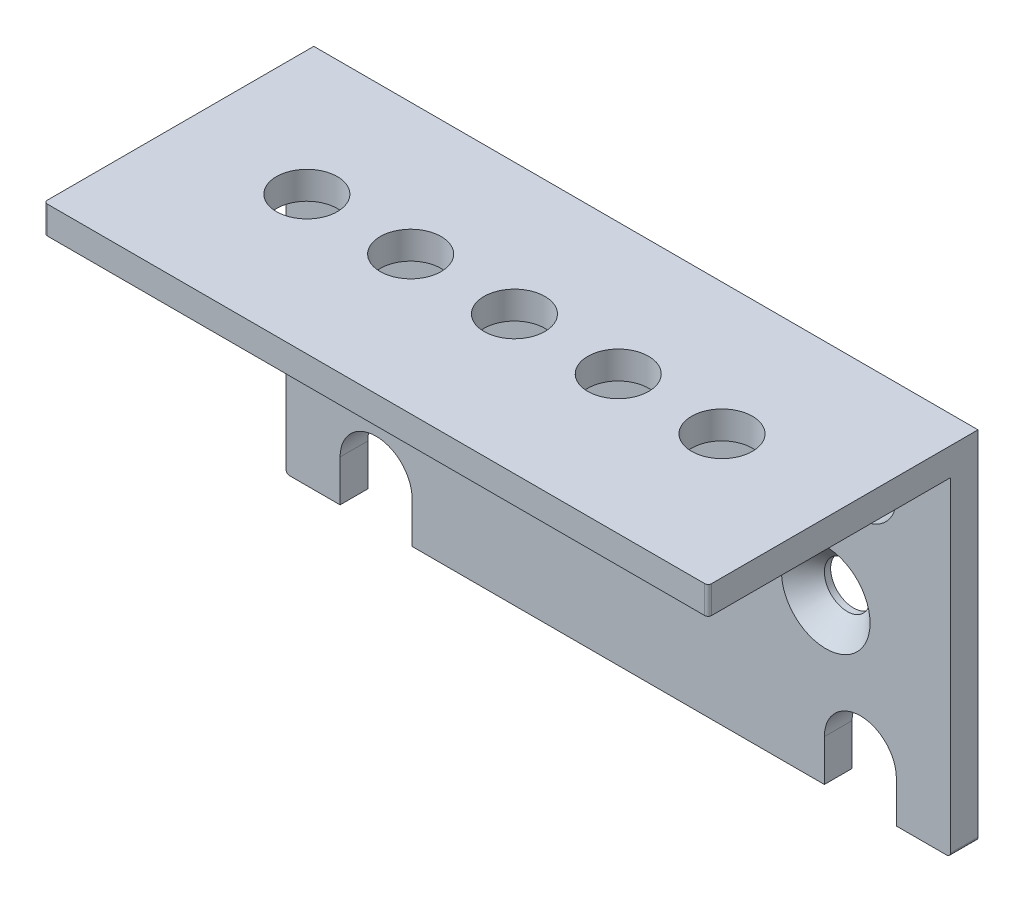
SolidWorks part; units mm, degrees
ref_plane "前视基准面" through (0, 0, 0) normal (0, 0, 1) x (1, 0, 0)
ref_plane "上视基准面" through (0, 0, 0) normal (0, 1, 0) x (1, 0, 0)
ref_plane "右视基准面" through (0, 0, 0) normal (1, 0, 0) x (0, 0, -1)
other "Configuration Table"
sketch "草图1" plane through (0, 0, 0) normal (0, 0, 1) x (1, 0, 0)
  line L0 (0, 0) -> (96, 0)
  line L1 (96, 0) -> (96, -47)
  line L2 (96, -47) -> (0, -47)
  line L3 (0, -47) -> (0, 0)
  dimension "D1" = 96
  dimension "D2" = 47
extrude "凸台-拉伸1" add sketch "草图1" along normal blind 4
sketch "草图2" plane through (0, 0, 4) normal (0, 0, 1) x (1, 0, 0)
  line L0 (96, -23.5) -> (0, -23.5)
  line L1 (96, -47) -> (96, 0) construction
  line L2 (0, 0) -> (0, -47) construction
  line L3 (48, 0) -> (48, -47)
  line L4 (96, 0) -> (0, 0) construction
  line L5 (0, -47) -> (96, -47) construction
  line L6 (48, -23.5) -> (48, -12)
  line L7 (18.2, -41) -> (18.2, -47)
  line L8 (0, -47) -> (96, -47) construction
  line L9 (18.2, -47) -> (7.8, -47)
  line L10 (7.8, -47) -> (7.8, -41)
  line L11 (77.8, -41) -> (77.8, -47)
  line L12 (77.8, -47) -> (88.2, -47)
  line L13 (88.2, -47) -> (88.2, -41)
  circle A0 centre (83, -6) radius 5.2
  circle A1 centre (83, -41) radius 5.2
  circle A2 centre (13, -41) radius 5.2
  circle A3 centre (13, -6) radius 5.2
  circle A4 centre (48, -23.5) radius 2.8224
  circle A5 centre (78, -23.5) radius 2.4023
  circle A6 centre (18, -23.5) radius 3.1016
  line M5 (0, -47) -> (96, -47)
  dimension "D1" = 35
  dimension "D3" = 30
  dimension "D4" = 30
  dimension "D2" = 17.5
sketch "草图8" plane through (0, 0, 4) normal (0, 0, 1) x (1, 0, 0)
  line L5 (48, -47) -> (48, 0)
  line L6 (0, -47) -> (96, -47) construction
  line L7 (96, 0) -> (0, 0) construction
  line L8 (96, -23.5) -> (0, -23.5)
  line L9 (96, -47) -> (96, 0) construction
  line L10 (0, 0) -> (0, -47) construction
  line L11 (48, -23.5) -> (78, -23.5)
  line L12 (48, -23.5) -> (18, -23.5)
  circle A0 centre (18, -23.5) radius 3.3648
  circle A1 centre (48, -23.5) radius 3.7667
  circle A2 centre (78, -23.5) radius 3.2192
  circle A3 centre (63, -23.5) radius 3.2586
  circle A4 centre (33, -23.5) radius 3.1199
  dimension "D3" = 15
  dimension "D1" = 30
  dimension "D2" = 60
  dimension "D4" = 15
sketch "草图12" plane through (0, 0, 0) normal (0, 1, 0) x (1, 0, 0)
  line L0 (0, -4) -> (0, 0)
  line L2 (96, -4) -> (96, 0)
  line L3 (0, -4) -> (96, -4)
  line L4 (0, 0) -> (96, 0)
  line L7 (0, -4) -> (0, -5)
  line L9 (96, 0) -> (96, -39)
  line L10 (0, 0) -> (0, -39)
  line L11 (48, -19) -> (78, -19)
  line L13 (0, -39) -> (96, -39)
  circle A3 centre (18, -19) radius 4.4
  circle A4 centre (78, -19) radius 4.4
  circle A5 centre (48, -19) radius 4.4
  circle A6 centre (63, -19) radius 4.4
  circle A7 centre (33, -19) radius 4.4
  line M7 (96, 0) -> (0, 0)
  line M8 (0, 0) -> (0, -4)
  line M9 (0, -4) -> (96, -4)
  line M10 (96, -4) -> (96, 0)
  dimension "D1" = 39
  dimension "D2" = 60
  dimension "D3" = 15
  dimension "D4" = 30
  dimension "D5" = 48
extrude "凸台-拉伸3" add sketch "草图12" along normal blind 4.5 contours L0 L3 M10 M7 M8 M9 | A6 A4 A5 L10 L13 L9 L3 A3 A7 M9 region at (48, 0, 2) region at (48, 0, 5.0218)
sketch "草图13" plane through (0, -47, 0) normal (0, -1, 0) x (1, 0, 0)
  line L0 (0, 4) -> (0, 0)
  line L1 (0, 0) -> (96, 0)
  line L2 (96, 0) -> (96, 4)
  line L3 (96, 4) -> (0, 4)
extrude "切除-拉伸1" cut sketch "草图12<4>" along normal blind 0.5 contours A6 A4 A5 L10 L13 L9 L3 A3 A7 M9 region at (48, 0, 5.0218)
sketch "草图12<4>" plane through (0, 0, 0) normal (0, 1, 0) x (1, 0, 0) same geometry as "草图12"
extrude "切除-拉伸2" cut sketch "草图2" against normal blind 10 contours A3 | A2 | A1 | A0 | L13 A1 L11 M5 | A2 L10 L7 M5 | A2 region at (77.9201, -44, 4) region at (13, -46.8799, 4) region at (13, -41, 4) region at (83, -41, 4) region at (83, -6, 4) region at (13, -6, 4)
hole_wizard "M6 内六角花形沉头螺钉的锥形沉头孔1" positions "草图14" profile "草图15" countersink size "M6" standard "GB" end condition through all
sketch "草图14" plane through (0, 0, 4) normal (0, 0, 1) x (1, 0, 0)
  point P0 (18, -23.5)
  point P3 (48, -23.5)
  point P6 (78, -23.5)
sketch "草图15" plane through (18, -23.5, 4) normal (1, 0, 0) x (0, -1, 0)
  line L0 (0, 0) -> (0, 4)
  line L1 (0, 4) -> (3.3, 4)
  line L2 (3.3, 4) -> (3.3, 3.1)
  line L3 (3.3, 3.1) -> (6.4, 0)
  line L5 (6.4, 0) -> (0, 0)
  line L6 (-3.3, 3.1) -> (-6.4, 0) construction
  line L11 (0, -6.35) -> (0, 107.95) construction
  dimension "通孔孔直径" = 6.6
  dimension "通孔孔深度" = 4
  dimension "近端锥形沉头孔直径" = 12.8
  dimension "近端锥形沉头孔角度" = 90
fillet "圆角1" radius 0.5 4 edges at (0, -47, 2) (96, -47, 2) (96, 2.5, 39) (0, 2.5, 39)
